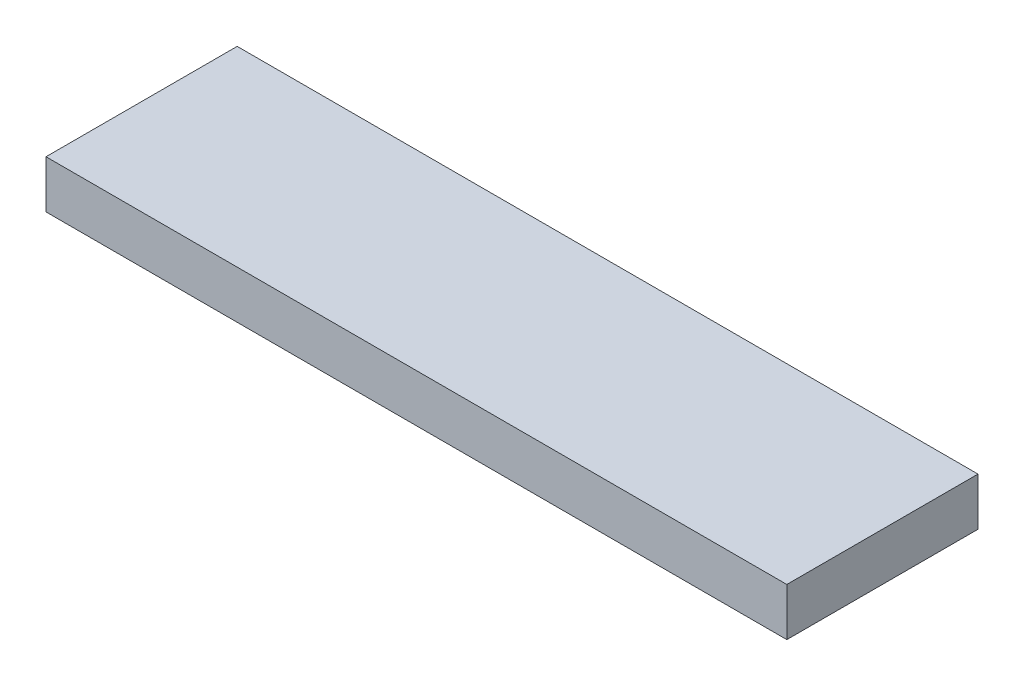
SolidWorks part; units mm, degrees
ref_plane "Front Plane" through (0, 0, 0) normal (0, 0, 1) x (1, 0, 0)
ref_plane "Top Plane" through (0, 0, 0) normal (0, 1, 0) x (1, 0, 0)
ref_plane "Right Plane" through (0, 0, 0) normal (1, 0, 0) x (0, 0, -1)
sketch "Sketch1" plane through (0, 0, 0) normal (0, 1, 0) x (1, 0, 0)
  line L0 (98.425, 25.4) -> (98.425, 0)
  line L1 (0, 0) -> (98.425, 0)
  line L2 (0, 0) -> (0, 25.4)
  line L3 (0, 25.4) -> (98.425, 25.4)
  line L4 (101.6, -13.453) -> (101.6, 25.4) construction
  dimension "D1" = 25.4
  dimension "D2" = 101.6
  dimension "D3" = 3.175
extrude "Boss-Extrude1" add sketch "Sketch1" along normal blind 6.35
